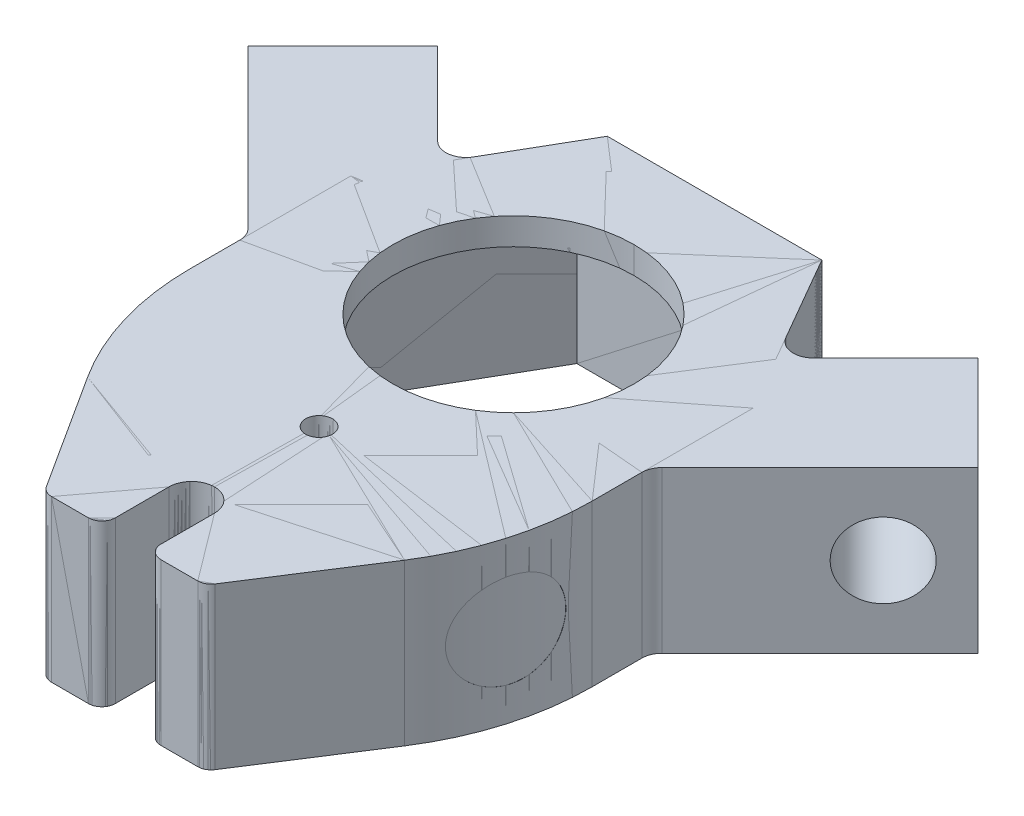
SolidWorks part; units mm, degrees
note: '?' marks a value the reader was unsure of.
ref_plane "Front Plane" through (0, 0, 0) normal (0, 0, 1) x (1, 0, 0)
ref_plane "Top Plane" through (0, 0, 0) normal (0, 1, 0) x (1, 0, 0)
ref_plane "Right Plane" through (0, 0, 0) normal (1, 0, 0) x (0, 0, -1)
ref_axis "Axis1" through (0, 14.8656, 0) along (0, -1, 0)?
sketch "Sketch1" plane through (0, 0, 0) normal (0, 1, 0) x (1, 0, 0)
  line L0 (0, 15) -> (0, -15) construction
  line L5 (-15, 15) -> (15, 15)
  line L7 (-15, 15) -> (-15, -15)
  line L10 (-15, -15) -> (15, -15)
  line L11 (15, 15) -> (15, -15)
  line L13 (6.4525, -11.176) -> (12.9049, 0)
  line L14 (12.9049, 0) -> (6.4525, 11.176)
  line L15 (6.4525, 11.176) -> (-6.4525, 11.176)
  line L16 (-6.4525, 11.176) -> (-12.9049, 0)
  line L17 (-12.9049, 0) -> (-6.4525, -11.176)
  line L18 (-6.4525, -11.176) -> (6.4525, -11.176)
  circle A0 centre (0, 0) radius 11.176 construction
  dimension "D3" = 15
  dimension "D4" = 22.352
  dimension "D1" = 30
  dimension "D2" = 30
extrude "Boss-Extrude1" add sketch "Sketch1" along normal blind 12
sketch "Sketch8" plane through (0, 0, 0) normal (0, 1, 0) x (1, 0, 0)
  line L0 (-15, -15) -> (15, -15) construction
  line L1 (-6, -15) -> (6, -15)
  line L2 (-6, -15) -> (-6, -29)
  line L3 (-6, -29) -> (-1.7, -29)
  line L4 (6, -15) -> (6, -29)
  line L5 (0, 0) -> (0, -30) construction
  line L6 (-1.7, -24) -> (-1.7, -29)
  line L7 (1.7, -24) -> (1.7, -29)
  line L8 (1.7, -29) -> (6, -29)
  arc A0 (1.7, -24) -> (-1.7, -24) centre (0, -24) ccw
  dimension "D2" = 3.4
  dimension "D1" = 24
  dimension "D3" = 5
  dimension "D4" = 12
extrude "Boss-Extrude6" add sketch "Sketch8" along normal up to surface (12 mm away) up to face at (0, 12, 0)
sketch "Sketch9" plane through (0, 12, 0) normal (0, 1, 0) x (1, 0, 0)
  line L27 (-14.637, 0) -> (-7.3185, -12.676)
  line L28 (-7.3185, -12.676) -> (7.3185, -12.676)
  line L29 (7.3185, -12.676) -> (14.637, 0)
  line L30 (14.637, 0) -> (7.3185, 12.676)
  line L31 (7.3185, 12.676) -> (-7.3185, 12.676)
  line L32 (-7.3185, 12.676) -> (-14.637, 0)
  line L33 (-14.637, 0) -> (-7.3185, -12.676)
  line L34 (-7.3185, -12.676) -> (7.3185, -12.676)
  line L35 (7.3185, -12.676) -> (14.637, 0)
  line L36 (14.637, 0) -> (7.3185, 12.676)
  line L37 (7.3185, 12.676) -> (-7.3185, 12.676)
  line L38 (-7.3185, 12.676) -> (-14.637, 0)
  circle A0 centre (0, 0) radius 9
  dimension "D2" = 18
  dimension "D1" = 1.5
extrude "Boss-Extrude7" [suppressed] add sketch "Sketch9" along normal blind 2
sketch "Sketch3" plane through (0, 12, 0) normal (0, 1, 0) x (1, 0, 0)
  line L1 (-5.25, -18.5) -> (5.25, -18.5)
  line L2 (-5.25, -18.5) -> (-5.25, -10.5)
  line L3 (-5.25, -10.5) -> (5.25, -10.5)
  line L4 (5.25, -18.5) -> (5.25, -10.5)
  line L5 (0, 0) -> (0, -30) construction
  line L6 (-5.25, -14.5) -> (5.25, -14.5) construction
  circle A0 centre (0, -14.5) radius 1
  dimension "D3" = 2
  dimension "D1" = 8
  dimension "D2" = 10.5
  dimension "D4" = 14.5
extrude "Boss-Extrude3" [suppressed] add sketch "Sketch3" along normal blind 10
sketch "Sketch5" [suppressed] plane through (5.25, 0, 0) normal (1, 0, 0) x (0, 0, -1)
  line L0 (-14.5, 20) -> (-14.5, 10) construction
  line L1 (-18.5, 20) -> (-10.5, 20) construction
  line L4 (-15, 10) -> (15, 10) construction
  circle A0 centre (-14.5, 15) radius 2
  dimension "D1" = 4
extrude "Cut-Extrude1" [suppressed] cut sketch "Sketch5" against normal blind 5
chamfer "Chamfer1" distance 7 angle 60 2 edges at (-15, 6, -15) (15, 6, -15)
sketch "Sketch6" plane through (0, 0, 0) normal (0, 1, 0) x (1, 0, 0)
  line L0 (0, 0) -> (0, -19.1236) construction
  line L1 (0, 0) -> (-11.2123, 11.2123) construction
  line L11 (-11.2123, 11.2123) -> (-21.1118, 1.3128) construction
  line L12 (-27.2236, 7.4246) -> (-15, -4.799)
  line L13 (-27.2236, 7.4246) -> (-20.1525, 14.4957)
  line L14 (-20.1525, 14.4957) -> (-12.6327, 6.9759)
  line L18 (-8, 15) -> (-15, 2.8756) construction
  line L19 (-15, 2.8756) -> (-15, -15) construction
  line L20 (-15, -4.799) -> (-15, 2.8756)
  line L21 (-15, 2.8756) -> (-12.6327, 6.9759)
  dimension "D1" = 45
  dimension "D3" = 24.5
  dimension "D4" = 10
  dimension "D5" = 14
extrude "Boss-Extrude4" add sketch "Sketch6" along normal up to surface (12 mm away) up to face at (0, 12, 13.3249)
sketch "Sketch7" plane through (-9.8995, 0, 9.8995) normal (-0.7071, 0, 0.7071) x (0.7071, 0, 0.7071)
  line L0 (-19.5, 12) -> (-19.5, 0) construction
  line L1 (-7.2132, 12) -> (-24.5, 12) construction
  line L2 (-7.2132, 0) -> (-24.5, 0) construction
  line L3 (-24.5, 12) -> (-24.5, 0) construction
  circle A0 centre (-19.5, 6) radius 2.8
  dimension "D1" = 5.6
  dimension "D2" = 5
extrude "Cut-Extrude2" cut sketch "Sketch7" against normal blind 15
chamfer "Chamfer2" distance 14 distance2 9 1 edges at (6, 6, 15)
chamfer "Chamfer3" distance 9 distance2 14 1 edges at (-6, 6, 15)
fillet "Fillet2" radius 20 2 edges at (-15, 6, 15) (15, 6, 15)
fillet "Fillet3" radius 1 4 edges at (1.7, 6, 29) (-1.7, 6, 29) (6, 6, 29) (-6, 6, 29)
draft "Draft1" [suppressed] type of draft neutral plane draft angle 10 faces to draft 2 parameters "D1"=10
draft "Draft2" [suppressed] type of draft neutral plane draft angle 5 faces to draft 7 parameters "D1"=5
fillet "Fillet4" radius 1.5 2 edges at (-12.6327, 6, -6.9759) (-15, 6, 4.799)
sketch "Sketch10" plane through (0, 12, 0) normal (0, 1, 0) x (1, 0, 0)
  circle A0 centre (0, -14.5) radius 1
  dimension "D2" = 2
  dimension "D1" = 14.5
extrude "Cut-Extrude3" cut sketch "Sketch10" against normal through all
sketch "Sketch11" plane through (0, 0, 0) normal (1, 0, 0) x (0, 0, -1)
  line L0 (-13.5, 12) -> (-15.5, 12) construction
  line L1 (-13.5, 12) -> (-15.5, 12) construction
  line L2 (-15.5, 0) -> (-13.5, 0) construction
  line L3 (-15.5, 0) -> (-13.5, 0) construction
  line L4 (-14.5, 12) -> (-14.5, 0) construction
  circle A0 centre (-14.5, 6) radius 2
  dimension "D1" = 4
extrude "Cut-Extrude4" cut sketch "Sketch11" along normal through all
sketch "Sketch12" plane through (0, 12, 0) normal (0, 1, 0) x (1, 0, 0)
  line L0 (6.4525, 11.176) -> (-6.4525, 11.176) construction
  line L1 (12.9049, 0) -> (6.4525, 11.176) construction
  line L2 (6.4525, -11.176) -> (12.9049, 0) construction
  line L3 (-6.4525, -11.176) -> (6.4525, -11.176) construction
  line L4 (-12.9049, 0) -> (-6.4525, -11.176) construction
  line L5 (-6.4525, 11.176) -> (-12.9049, 0) construction
  line L6 (6.4525, 11.176) -> (-6.4525, 11.176)
  line L7 (12.9049, 0) -> (6.4525, 11.176)
  line L8 (6.4525, -11.176) -> (12.9049, 0)
  line L9 (-6.4525, -11.176) -> (6.4525, -11.176)
  line L10 (-12.9049, 0) -> (-6.4525, -11.176)
  line L11 (-6.4525, 11.176) -> (-12.9049, 0)
  circle A0 centre (0, 0) radius 9
  dimension "D1" = 18
extrude "Boss-Extrude8" add sketch "Sketch12" against normal offset from surface (2 mm away) 10 up to face at (0, 0, 15.5)
sketch "Sketch13" plane through (15, 0, 0) normal (1, 0, 0) x (0, 0, -1)
  circle A0 centre (-14.5, 6) radius 3.5
  dimension "D1" = 7
extrude "Cut-Extrude5" cut sketch "Sketch13" against normal blind 8
mirror "Mirror2" about plane through (0, 0, 0) normal (1, 0, 0) of bodies 121
